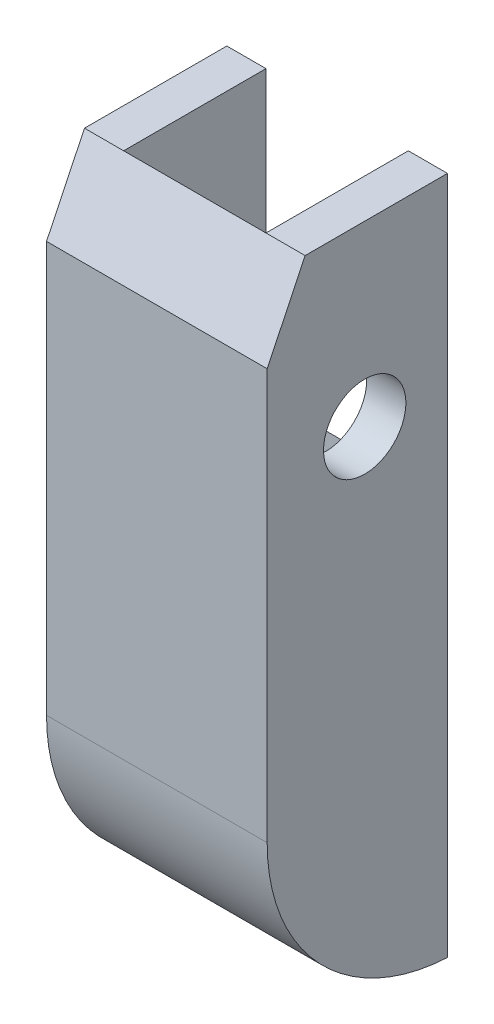
SolidWorks part; units mm, degrees
ref_plane "Front Plane" through (0, 0, 0) normal (0, 0, 1) x (1, 0, 0)
ref_plane "Top Plane" through (0, 0, 0) normal (0, 1, 0) x (1, 0, 0)
ref_plane "Right Plane" through (0, 0, 0) normal (1, 0, 0) x (0, 0, -1)
sketch "Sketch1" plane through (0, 0, 0) normal (0, 0, 1) x (1, 0, 0)
  line L1 (0, 0) -> (11.811, 0)
  line L2 (0, 0) -> (0, 45.9892)
  line L3 (0, 45.9892) -> (11.811, 45.9892)
  line L4 (11.811, 0) -> (11.811, 45.9892)
  dimension "D1" = 11.811
  dimension "D2" = 45.9892
extrude "Boss-Extrude1" add sketch "Sketch1" along normal blind 9.652 contours L2 L3 L4 L1
fillet "Fillet5" radius 4.826 1 edges at (5.9055, 45.9892, 0)
sketch "Sketch2" plane through (0, 0, 0) normal (0, 0, -1) x (-1, 0, 0)
  line L0 (0, 45.9892) -> (-11.811, 45.9892) construction
  line L1 (-9.7155, 45.9892) -> (-2.0955, 45.9892)
  line L2 (-9.7155, 45.9892) -> (-9.7155, 23.6372)
  line L3 (-9.7155, 23.6372) -> (-2.0955, 23.6372)
  line L4 (-2.0955, 45.9892) -> (-2.0955, 23.6372)
  line L5 (0, 0) -> (0, 41.1632) construction
  dimension "D1" = 22.352
  dimension "D2" = 7.62
  dimension "D3" = 2.0955
extrude "Cut-Extrude1" cut sketch "Sketch2" against normal blind 7.62
sketch "Sketch3" plane through (0, 0, 0) normal (-1, 0, 0) x (0, 0, 1)
  line L0 (7.62, 45.9892) -> (7.62, 23.6372) construction
  line L2 (7.62, 23.6372) -> (0, 23.6372) construction
  circle A0 centre (4.4323, 26.8249) radius 2.2035
  dimension "D1" = 3.1877
  dimension "D3" = 4.4069
  dimension "D2" = 3.1877
extrude "Cut-Extrude2" cut sketch "Sketch3" against normal through all and the other way through all
fillet "Fillet4" radius 4.826 1 edges at (5.9055, 45.9892, 9.652)
fillet "Fillet6" radius 10.16 1 edges at (5.9055, 0, 9.652)
sketch "Sketch4" plane through (11.811, 0, 0) normal (1, 0, 0) x (0, 0, -1)
  line L0 (-9.652, 32.1188) -> (-7.62, 36.3499)
  line L1 (-9.652, 10.1473) -> (-9.652, 41.1632) construction
  line L2 (-7.62, 36.3499) -> (0, 36.3499)
  line L3 (0, 0) -> (0, 41.1632) construction
  line L4 (-9.652, 32.1188) -> (-9.652, 45.9892)
  line L5 (-9.652, 45.9892) -> (0, 45.9892)
  line L6 (0, 45.9892) -> (0, 36.3499)
  line L7 (-0.4369, 28.7437) -> (4.2626, 18.9582) construction
  line L8 (-4.4323, 26.8249) -> (0, 26.8249) construction
  line L9 (-4.4323, 26.8249) -> (-0.4369, 28.7437) construction
  line L10 (-4.4323, 26.8249) -> (-0.4369, 24.9061) construction
  arc A0 (-4.826, 45.9892) -> (-9.652, 41.1632) centre (-4.826, 41.1632) ccw construction
  circle A1 centre (7.1247, 20.3327) radius 3.175 construction
  point P14 (-4.4323, 26.8249)
  point P22 (0, 0)
  point P23 (0, 0)
  dimension "D2" = 6.35
  dimension "D1" = 9.525
  dimension "D3" = 11.557
  dimension "D4" = 6.4922
extrude "Cut-Extrude3" cut sketch "Sketch4" against normal through all
sketch "Sketch5" plane through (9.7155, 0, 0) normal (-1, 0, 0) x (0, 0, 1)
  line L0 (5.1581, 23.6372) -> (0, 21.1601)
  line L1 (0, 21.1601) -> (0, 23.6372)
  line L2 (0, 23.6372) -> (5.1581, 23.6372)
  line L3 (4.4323, 26.8249) -> (0.4369, 24.9061) construction
  line L4 (4.4323, 26.8249) -> (7.62, 26.8249) construction
  line L5 (4.4323, 26.8249) -> (5.8123, 23.9514) construction
  line L6 (7.62, 36.3499) -> (7.62, 23.6372) construction
  line L7 (5.8123, 23.9514) -> (5.1581, 23.6372)
  line L8 (7.62, 26.8249) -> (7.62, 23.6372)
  line L9 (7.62, 23.6372) -> (5.1581, 23.6372)
  arc A0 (5.8123, 23.9514) -> (7.62, 26.8249) centre (4.4323, 26.8249) ccw
  point P2 (7.62, 26.845)
  point P13 (0, 0)
  line M4 (7.62, 23.6372) -> (7.62, 36.3499)
  line M7 (0, 23.6372) -> (7.62, 23.6372)
extrude "Cut-Extrude4" cut sketch "Sketch5" along normal up to surface (7.62 mm away) contours L1 L0 M7 region at (9.7155, 22.8115, 1.7194) up to face at (2.0955, 24.6215, 4.4323)
extrude "Boss-Extrude2" add sketch "Sketch5<3>" along normal up to surface (7.62 mm away) contours A0 L7 M7 M4 region at (9.7155, 24.361, 6.9399) up to face at (2.0955, 24.6215, 4.4323)
sketch "Sketch5<3>" plane through (9.7155, 0, 0) normal (-1, 0, 0) x (0, 0, 1) same geometry as "Sketch5"
